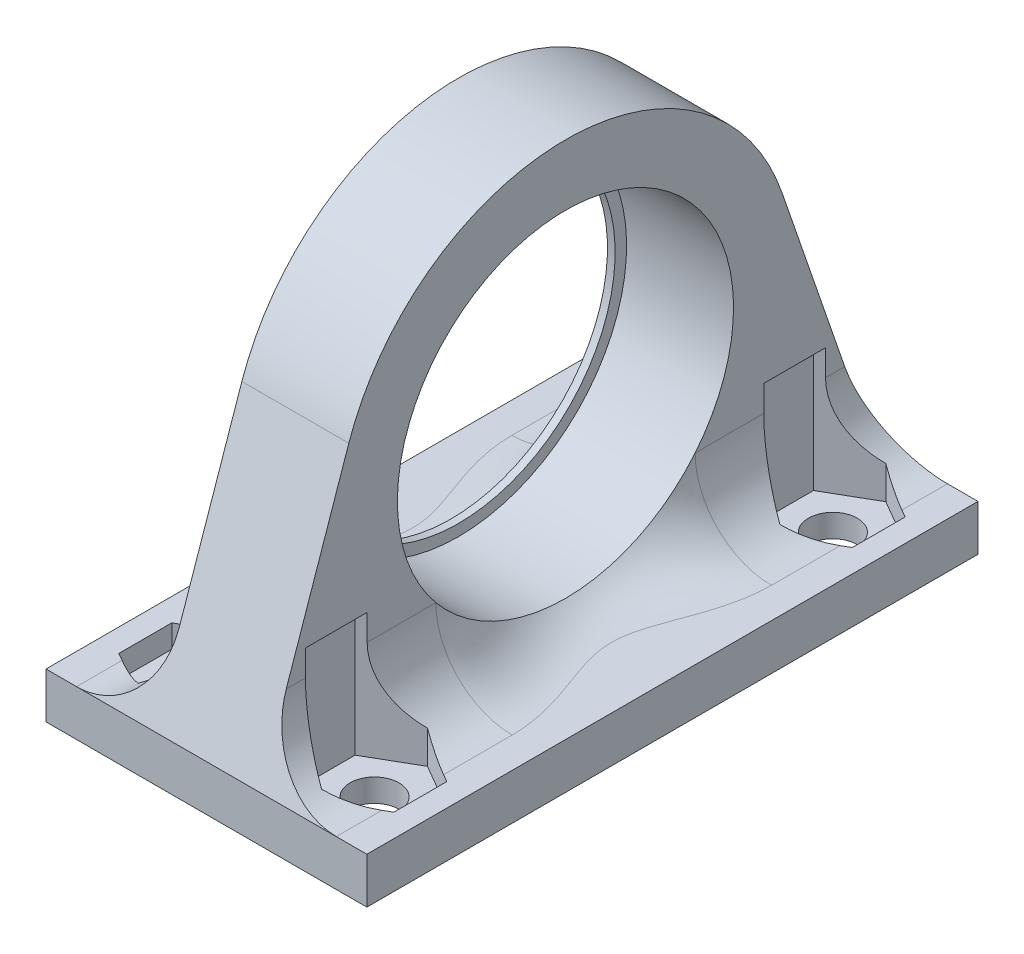
SolidWorks part; units mm, degrees
ref_plane "前基準面" through (0, 0, 0) normal (0, 0, 1) x (1, 0, 0)
ref_plane "上基準面" through (0, 0, 0) normal (0, 1, 0) x (1, 0, 0)
ref_plane "右基準面" through (0, 0, 0) normal (1, 0, 0) x (0, 0, -1)
sketch "草圖1" plane through (0, 0, 0) normal (0, 1, 0) x (1, 0, 0)
  line L1 (-10.5, -20) -> (10.5, -20)
  line L2 (-10.5, -20) -> (-10.5, 20)
  line L3 (-10.5, 20) -> (10.5, 20)
  line L4 (10.5, -20) -> (10.5, 20)
  line L5 (0, 20) -> (0, -20) construction
  line L6 (-10.5, 0) -> (10.5, 0) construction
  circle A0 centre (-6, 15) radius 1.6
  circle A1 centre (6, 15) radius 1.6
  circle A2 centre (-6, -15) radius 1.6
  circle A3 centre (6, -15) radius 1.6
  point P0 (0, 0)
  dimension "D2" = 3.2
  dimension "D1" = 12
  dimension "D3" = 30
  dimension "D4" = 40
  dimension "D5" = 21
extrude "填料-伸長1" add sketch "草圖1" along normal blind 3
sketch "草圖2" plane through (0, 0, 0) normal (1, 0, 0) x (0, 0, -1)
  line L0 (0, -9.6631) -> (0, 9.6631) construction
  line L2 (-14.1818, 19.8863) -> (-20, 3)
  line L3 (-20, 3) -> (20, 3)
  line L4 (14.1818, 19.8863) -> (20, 3)
  line L5 (-20, 3) -> (20, 3) construction
  circle A0 centre (0, 15) radius 11
  arc A1 (-14.1818, 19.8863) -> (14.1818, 19.8863) centre (0, 15) cw
  point P6 (0, 0)
  point P11 (0, 3)
  dimension "D1" = 22
  dimension "D2" = 15
  dimension "D3" = 15
extrude "填料-伸長2" add sketch "草圖2" along normal mid plane 7
fillet "圓角1" radius 5 2 edges at (-3.5, 3, 0) (3.5, 3, 0)
sketch "草圖3" plane through (0, 3, 0) normal (0, 1, 0) x (1, 0, 0)
  line L0 (0, -28.9462) -> (0, 28.9462) construction
  line L1 (-6, 11.5359) -> (-3, 13.2679)
  line L2 (-3, 13.2679) -> (-3, 16.7321)
  line L3 (-3, 16.7321) -> (-6, 18.4641)
  line L4 (-6, 18.4641) -> (-9, 16.7321)
  line L5 (-9, 16.7321) -> (-9, 13.2679)
  line L6 (-9, 13.2679) -> (-6, 11.5359)
  line L7 (-21.6301, 0) -> (21.6301, 0) construction
  line L8 (9, 13.2679) -> (6, 11.5359)
  line L9 (9, 16.7321) -> (9, 13.2679)
  line L10 (6, 18.4641) -> (9, 16.7321)
  line L11 (3, 16.7321) -> (6, 18.4641)
  line L12 (3, 13.2679) -> (3, 16.7321)
  line L13 (6, 11.5359) -> (3, 13.2679)
  line L14 (6, -11.5359) -> (3, -13.2679)
  line L15 (3, -13.2679) -> (3, -16.7321)
  line L16 (3, -16.7321) -> (6, -18.4641)
  line L17 (6, -18.4641) -> (9, -16.7321)
  line L18 (9, -16.7321) -> (9, -13.2679)
  line L19 (9, -13.2679) -> (6, -11.5359)
  line L20 (-9, -13.2679) -> (-6, -11.5359)
  line L21 (-9, -16.7321) -> (-9, -13.2679)
  line L22 (-6, -18.4641) -> (-9, -16.7321)
  line L23 (-3, -16.7321) -> (-6, -18.4641)
  line L24 (-3, -13.2679) -> (-3, -16.7321)
  line L25 (-6, -11.5359) -> (-3, -13.2679)
  circle A0 centre (-6, 15) radius 3 construction
  circle A1 centre (6, 15) radius 3 construction
  circle A2 centre (6, -15) radius 3 construction
  circle A3 centre (-6, -15) radius 3 construction
  point P13 (0, 0)
  point P16 (0, 0)
  dimension "D1" = 6
extrude "除料-伸長2" cut sketch "草圖3" against normal blind 1.5 and the other way blind 6.7
sketch "草圖4" plane through (-3.5, 0, 0) normal (-1, 0, 0) x (0, 0, 1)
  line L0 (0, -35.6834) -> (0, 35.6834) construction
  circle A0 centre (0, 15) radius 11 construction
  circle A1 centre (0, 15) radius 11.75
  circle A4 centre (0, 15) radius 10.25
  arc A5 (8.4853, 8) -> (-8.4853, 8) centre (0, 15) ccw construction
  point P6 (0, 0)
  dimension "D1" = 0.75
  dimension "D2" = 0.75
extrude "填料-伸長3" add sketch "草圖4" along normal blind 0.5 separate body
